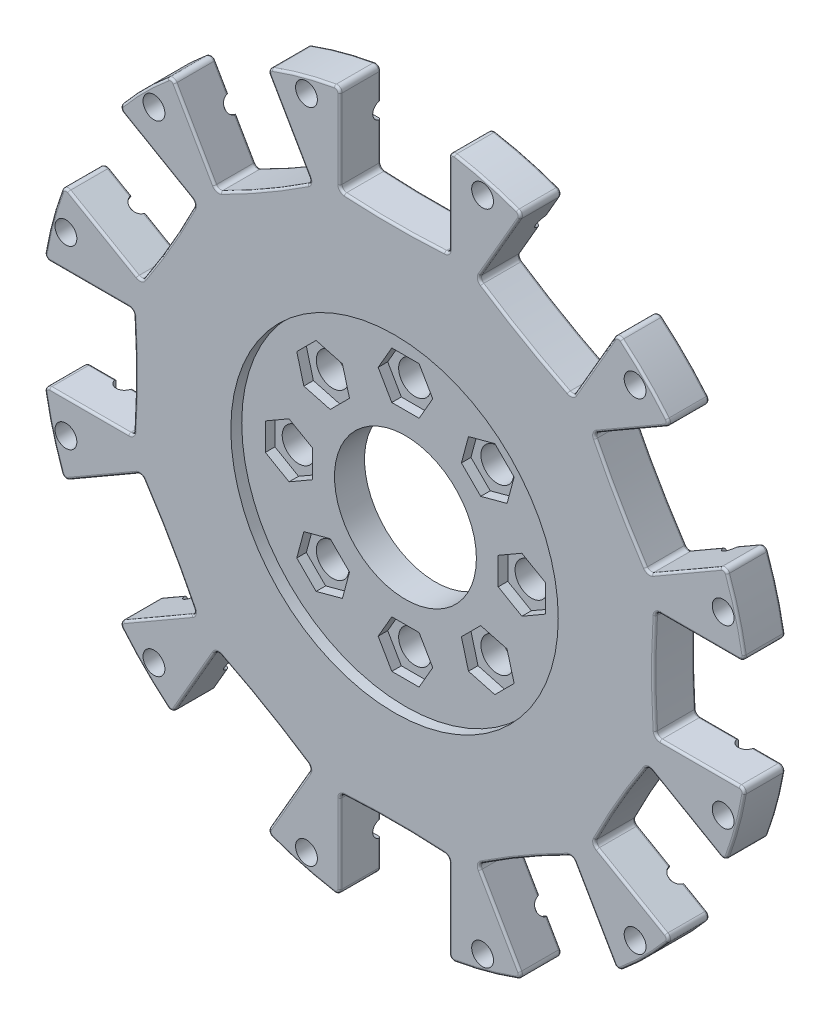
SolidWorks part; units mm, degrees
ref_plane "Front Plane" through (0, 0, 0) normal (0, 0, 1) x (1, 0, 0)
ref_plane "Top Plane" through (0, 0, 0) normal (0, 1, 0) x (1, 0, 0)
ref_plane "Right Plane" through (0, 0, 0) normal (1, 0, 0) x (0, 0, -1)
sketch "Sketch2" plane through (0, 0, 0) normal (0, 0, 1) x (1, 0, 0)
  line L0 (-10, 64.2262) -> (-10, 47.8337)
  line L1 (10, 64.2262) -> (10, 47.8337)
  line L2 (23.4528, 60.6215) -> (15.2566, 46.4252)
  line L3 (40.7733, 50.6215) -> (32.5771, 36.4252)
  line L4 (50.6215, 40.7733) -> (36.4252, 32.5771)
  line L5 (60.6215, 23.4528) -> (46.4252, 15.2566)
  line L6 (64.2262, 10) -> (47.8337, 10)
  line L7 (64.2262, -10) -> (47.8337, -10)
  line L8 (60.6215, -23.4528) -> (46.4252, -15.2566)
  line L9 (50.6215, -40.7733) -> (36.4252, -32.5771)
  line L10 (40.7733, -50.6215) -> (32.5771, -36.4252)
  line L11 (23.4528, -60.6215) -> (15.2566, -46.4252)
  line L12 (10, -64.2262) -> (10, -47.8337)
  line L13 (-10, -64.2262) -> (-10, -47.8337)
  line L14 (-23.4528, -60.6215) -> (-15.2566, -46.4252)
  line L15 (-40.7733, -50.6215) -> (-32.5771, -36.4252)
  line L16 (-50.6215, -40.7733) -> (-36.4252, -32.5771)
  line L17 (-60.6215, -23.4528) -> (-46.4252, -15.2566)
  line L18 (-64.2262, -10) -> (-47.8337, -10)
  line L19 (-64.2262, 10) -> (-47.8337, 10)
  line L20 (-60.6215, 23.4528) -> (-46.4252, 15.2566)
  line L21 (-50.6215, 40.7733) -> (-36.4252, 32.5771)
  line L22 (-40.7733, 50.6215) -> (-32.5771, 36.4252)
  line L23 (-23.4528, 60.6215) -> (-15.2566, 46.4252)
  arc A0 (-10, 64.2262) -> (-23.4528, 60.6215) centre (0, 0) ccw
  circle A1 centre (0, 0) radius 47.5
  arc A2 (-10, 47.8337) -> (10, 47.8337) centre (0, 197.5) ccw
  arc A3 (15.2566, 46.4252) -> (32.5771, 36.4252) centre (98.75, 171.04) ccw
  arc A4 (36.4252, 32.5771) -> (46.4252, 15.2566) centre (171.04, 98.75) ccw
  arc A5 (47.8337, 10) -> (47.8337, -10) centre (197.5, 0) ccw
  arc A6 (46.4252, -15.2566) -> (36.4252, -32.5771) centre (171.04, -98.75) ccw
  arc A7 (32.5771, -36.4252) -> (15.2566, -46.4252) centre (98.75, -171.04) ccw
  arc A8 (10, -47.8337) -> (-10, -47.8337) centre (0, -197.5) ccw
  arc A9 (-15.2566, -46.4252) -> (-32.5771, -36.4252) centre (-98.75, -171.04) ccw
  arc A10 (-36.4252, -32.5771) -> (-46.4252, -15.2566) centre (-171.04, -98.75) ccw
  arc A11 (-47.8337, -10) -> (-47.8337, 10) centre (-197.5, 0) ccw
  arc A12 (-46.4252, 15.2566) -> (-36.4252, 32.5771) centre (-171.04, 98.75) ccw
  arc A13 (-32.5771, 36.4252) -> (-15.2566, 46.4252) centre (-98.75, 171.04) ccw
  arc A14 (-40.7733, 50.6215) -> (-50.6215, 40.7733) centre (0, 0) ccw
  arc A15 (-60.6215, 23.4528) -> (-64.2262, 10) centre (0, 0) ccw
  arc A16 (-64.2262, -10) -> (-60.6215, -23.4528) centre (0, 0) ccw
  arc A17 (-50.6215, -40.7733) -> (-40.7733, -50.6215) centre (0, 0) ccw
  arc A18 (-23.4528, -60.6215) -> (-10, -64.2262) centre (0, 0) ccw
  arc A19 (10, -64.2262) -> (23.4528, -60.6215) centre (0, 0) ccw
  arc A20 (40.7733, -50.6215) -> (50.6215, -40.7733) centre (0, 0) ccw
  arc A21 (60.6215, -23.4528) -> (64.2262, -10) centre (0, 0) ccw
  arc A22 (64.2262, 10) -> (60.6215, 23.4528) centre (0, 0) ccw
  arc A23 (50.6215, 40.7733) -> (40.7733, 50.6215) centre (0, 0) ccw
  arc A24 (23.4528, 60.6215) -> (10, 64.2262) centre (0, 0) ccw
  point P66 (0, 0)
  dimension "D1" = 130
  dimension "D4" = 95
  dimension "D5" = 150
  dimension "D2" = 20
  dimension "D3" = 10
  dimension "D6" = 12
extrude "Boss-Extrude1" add sketch "Sketch2" along normal blind 7.5 contours A1 | L2 A24 L1 A2 A1 A3 | L4 A23 L3 A3 A1 A4 | L6 A22 L5 A4 A1 A5 | L8 A21 L7 A5 A1 A6 | L10 A20 L9 A6 A1 A7 | L12 A19 L11 A7 A1 A8 | L14 A18 L13 A8 A1 A9 | L16 A17 L15 A9 A1 A10 | L18 A16 L17 A10 A1 A11 | L20 A15 L19 A11 A1 A12 | L22 A14 L21 A12 A1 A13 | A13 A1 A2 L0 A0 L23 region at (-14.7728, 55.1327, 0) region at (14.7728, 55.1327, 0) region at (0, 0, 0) region at (40.3599, 40.3599, 0) region at (-40.3599, 40.3599, 0) region at (55.1327, 14.7728, 0) region at (-55.1327, 14.7728, 0) region at (55.1327, -14.7728, 0) region at (-55.1327, -14.7728, 0) region at (40.3599, -40.3599, 0) region at (-40.3599, -40.3599, 0) region at (14.7728, -55.1327, 0) region at (-14.7728, -55.1327, 0)
sketch "Sketch3" plane through (0, 0, 7.5) normal (0, 0, 1) x (1, 0, 0)
  line L0 (0, 0) -> (0, 47.5) construction
  line L49 (0, 0) -> (45.9619, 45.9619) construction
  line L62 (18.6194, 11.5483) -> (19.9135, 16.3779)
  line L63 (5, 21.3318) -> (2.5, 25.6619)
  line L64 (2.5, 25.6619) -> (-2.5, 25.6619)
  line L65 (-2.5, 25.6619) -> (-5, 21.3318)
  line L66 (-5, 21.3318) -> (-2.5, 17.0016)
  line L67 (-2.5, 17.0016) -> (2.5, 17.0016)
  line L68 (2.5, 17.0016) -> (5, 21.3318)
  line L69 (19.9135, 16.3779) -> (16.3779, 19.9135)
  line L70 (16.3779, 19.9135) -> (11.5483, 18.6194)
  line L71 (11.5483, 18.6194) -> (10.2542, 13.7897)
  line L72 (10.2542, 13.7897) -> (13.7897, 10.2542)
  line L73 (13.7897, 10.2542) -> (18.6194, 11.5483)
  line L74 (21.3318, -5) -> (25.6619, -2.5)
  line L75 (25.6619, -2.5) -> (25.6619, 2.5)
  line L76 (25.6619, 2.5) -> (21.3318, 5)
  line L77 (21.3318, 5) -> (17.0016, 2.5)
  line L78 (17.0016, 2.5) -> (17.0016, -2.5)
  line L79 (17.0016, -2.5) -> (21.3318, -5)
  line L80 (11.5483, -18.6194) -> (16.3779, -19.9135)
  line L81 (16.3779, -19.9135) -> (19.9135, -16.3779)
  line L82 (19.9135, -16.3779) -> (18.6194, -11.5483)
  line L83 (18.6194, -11.5483) -> (13.7897, -10.2542)
  line L84 (13.7897, -10.2542) -> (10.2542, -13.7897)
  line L85 (10.2542, -13.7897) -> (11.5483, -18.6194)
  line L86 (-5, -21.3318) -> (-2.5, -25.6619)
  line L87 (-2.5, -25.6619) -> (2.5, -25.6619)
  line L88 (2.5, -25.6619) -> (5, -21.3318)
  line L89 (5, -21.3318) -> (2.5, -17.0016)
  line L90 (2.5, -17.0016) -> (-2.5, -17.0016)
  line L91 (-2.5, -17.0016) -> (-5, -21.3318)
  line L92 (-18.6194, -11.5483) -> (-19.9135, -16.3779)
  line L93 (-19.9135, -16.3779) -> (-16.3779, -19.9135)
  line L94 (-16.3779, -19.9135) -> (-11.5483, -18.6194)
  line L95 (-11.5483, -18.6194) -> (-10.2542, -13.7897)
  line L96 (-10.2542, -13.7897) -> (-13.7897, -10.2542)
  line L97 (-13.7897, -10.2542) -> (-18.6194, -11.5483)
  line L98 (-21.3318, 5) -> (-25.6619, 2.5)
  line L99 (-25.6619, 2.5) -> (-25.6619, -2.5)
  line L100 (-25.6619, -2.5) -> (-21.3318, -5)
  line L101 (-21.3318, -5) -> (-17.0016, -2.5)
  line L102 (-17.0016, -2.5) -> (-17.0016, 2.5)
  line L103 (-17.0016, 2.5) -> (-21.3318, 5)
  line L104 (-11.5483, 18.6194) -> (-16.3779, 19.9135)
  line L105 (-16.3779, 19.9135) -> (-19.9135, 16.3779)
  line L106 (-19.9135, 16.3779) -> (-18.6194, 11.5483)
  line L107 (-18.6194, 11.5483) -> (-13.7897, 10.2542)
  line L108 (-13.7897, 10.2542) -> (-10.2542, 13.7897)
  line L109 (-10.2542, 13.7897) -> (-11.5483, 18.6194)
  circle A0 centre (0, 0) radius 30
  circle A1 centre (0, 0) radius 13
  arc A2 (-10, 47.8337) -> (10, 47.8337) centre (0, 197.5) ccw construction
  circle A3 centre (0, 21.3318) radius 5 construction
  arc A4 (50.6215, 40.7733) -> (40.7733, 50.6215) centre (0, 0) ccw construction
  circle A5 centre (44.0798, 44.0798) radius 2
  circle A6 centre (60.2141, 16.1343) radius 2
  circle A7 centre (60.2141, -16.1343) radius 2
  circle A8 centre (44.0798, -44.0798) radius 2
  circle A9 centre (16.1343, -60.2141) radius 2
  circle A10 centre (-16.1343, -60.2141) radius 2
  circle A11 centre (-44.0798, -44.0798) radius 2
  circle A12 centre (-60.2141, -16.1343) radius 2
  circle A13 centre (-60.2141, 16.1343) radius 2
  circle A14 centre (-44.0798, 44.0798) radius 2
  circle A15 centre (-16.1343, 60.2141) radius 2
  circle A16 centre (16.1343, 60.2141) radius 2
  circle A17 centre (0, 21.3318) radius 3
  circle A18 centre (15.0838, 15.0838) radius 3
  circle A19 centre (21.3318, 0) radius 3
  circle A20 centre (15.0838, -15.0838) radius 3
  circle A21 centre (0, -21.3318) radius 3
  circle A22 centre (-15.0838, -15.0838) radius 3
  circle A23 centre (-21.3318, 0) radius 3
  circle A24 centre (-15.0838, 15.0838) radius 3
  point P62 (0, 0)
  point P90 (0, 0)
  point P130 (0, 0)
  dimension "D1" = 8
  dimension "D3" = 12
extrude "Cut-Extrude1" cut sketch "Sketch3" against normal blind 3.75 contours L109 L104 L105 L106 L107 L108 | L68 L63 L64 L65 L66 L67 | L73 L62 L69 L70 L71 L72 | L76 L77 L78 L79 L74 L75 | L83 L84 L85 L80 L81 L82 | L90 L91 L86 L87 L88 L89 | L95 L96 L97 L92 L93 L94 | L102 L103 L98 L99 L100 L101
extrude "Cut-Extrude2" cut sketch "Sketch3<3>" against normal through all contours A24 | A19 | A20 | A21 | A22 | A23 | A1 | A17 | A18 | A13 | A14 | A15 | A16 | A5 | A6 | A7 | A8 | A9 | A10 | A11 | A12 region at (0, 0, 7.5) region at (21.3318, 0, 7.5) region at (15.0838, -15.0838, 7.5) region at (0, -21.3318, 7.5) region at (-15.0838, -15.0838, 7.5) region at (-21.3318, 0, 7.5) region at (-15.0838, 15.0838, 7.5)
sketch "Sketch3<3>" plane through (0, 0, 7.5) normal (0, 0, 1) x (1, 0, 0) same geometry as "Sketch3"
extrude "Cut-Extrude3" cut sketch "Sketch3<4>" against normal blind 2 contours A0
sketch "Sketch3<4>" plane through (0, 0, 7.5) normal (0, 0, 1) x (1, 0, 0) same geometry as "Sketch3"
sketch "Sketch8" plane through (0, 0, 0) normal (0, 0, -1) x (-1, 0, 0)
  line L0 (-12, 57) -> (12, 57) construction
  line L1 (-12, 57) -> (-12, 58.5)
  line L2 (-12, 58.5) -> (12, 58.5)
  line L3 (12, 58.5) -> (12, 57)
  line L4 (-12, 57) -> (12, 57)
  point P2 (0, 57)
  dimension "D1" = 24
  dimension "D2" = 57
  dimension "D3" = 1.5
revolve "Cut-Revolve2" cut sketch "Sketch8" angle 360 about L0
pattern_circular "CirPattern1" count 12 over 360 about axis through (0, 0, 0) along (0, 0, 1) of "Cut-Revolve2"
fillet "Fillet1" radius 0.9 48 edges at (64.2262, -10, 3.75) (60.6215, -23.4528, 3.75) (46.4252, -15.2566, 3.75) (36.4252, -32.5771, 3.75) (50.6215, -40.7733, 3.75) (40.7733, -50.6215, 3.75) (32.5771, -36.4252, 3.75) (15.2566, -46.4252, 3.75) (23.4528, -60.6215, 3.75) (10, -64.2262, 3.75) (10, -47.8337, 3.75) (-10, -47.8337, 3.75) (-10, -64.2262, 3.75) (-23.4528, -60.6215, 3.75) (-15.2566, -46.4252, 3.75) (-32.5771, -36.4252, 3.75) (-40.7733, -50.6215, 3.75) (-50.6215, -40.7733, 3.75) (-36.4252, -32.5771, 3.75) (-46.4252, -15.2566, 3.75) (-60.6215, -23.4528, 3.75) (-64.2262, -10, 3.75) (-47.8337, -10, 3.75) (-47.8337, 10, 3.75) (-64.2262, 10, 3.75) (-60.6215, 23.4528, 3.75) (-46.4252, 15.2566, 3.75) (-36.4252, 32.5771, 3.75) (-50.6215, 40.7733, 3.75) (-40.7733, 50.6215, 3.75) (-32.5771, 36.4252, 3.75) (-15.2566, 46.4252, 3.75) (-23.4528, 60.6215, 3.75) (-10, 64.2262, 3.75) (-10, 47.8337, 3.75) (10, 47.8337, 3.75) (10, 64.2262, 3.75) (23.4528, 60.6215, 3.75) (15.2566, 46.4252, 3.75) (32.5771, 36.4252, 3.75) (40.7733, 50.6215, 3.75) (36.4252, 32.5771, 3.75) (46.4252, 15.2566, 3.75) (60.6215, 23.4528, 3.75) (64.2262, 10, 3.75) (47.8337, 10, 3.75) (47.8337, -10, 3.75) (50.6215, 40.7733, 3.75)
fillet "Fillet2" radius 0.4 216 edges at (48.0613, -9.7555, 0) (48.0613, 9.7555, 0) (63.8548, 10.3202, 0) (60.46, 22.9898, 0) (46.5001, 15.5821, 0) (36.7445, 32.4792, 0) (32.4792, 36.7445, 0) (15.5821, 46.5001, 0) (22.9898, 60.46, 0) (10.3202, 63.8548, 0) (9.7555, 48.0613, 0) (-9.7555, 48.0613, 0) (-10.3202, 63.8548, 0) (-22.9898, 60.46, 0) (-15.5821, 46.5001, 0) (-32.4792, 36.7445, 0) (-40.865, 50.1398, 0) (-50.1398, 40.865, 0) (-36.7445, 32.4792, 0) (-46.5001, 15.5821, 0) (-60.46, 22.9898, 0) (-63.8548, 10.3202, 0) (-48.0613, 9.7555, 0) (-48.0613, -9.7555, 0) (-63.8548, -10.3202, 0) (-60.46, -22.9898, 0) (-46.5001, -15.5821, 0) (-36.7445, -32.4792, 0) (-50.1398, -40.865, 0) (-40.865, -50.1398, 0) (-32.4792, -36.7445, 0) (-15.5821, -46.5001, 0) (-22.9898, -60.46, 0) (-10.3202, -63.8548, 0) (-9.7555, -48.0613, 0) (9.7555, -48.0613, 0) (10.3202, -63.8548, 0) (22.9898, -60.46, 0) (15.5821, -46.5001, 0) (32.4792, -36.7445, 0) (40.865, -50.1398, 0) (50.1398, -40.865, 0) (36.7445, -32.4792, 0) (46.5001, -15.5821, 0) (60.46, -22.9898, 0) (63.8548, -10.3202, 0) (60.46, -22.9898, 7.5) (46.5001, -15.5821, 7.5) (36.7445, -32.4792, 7.5) (50.1398, -40.865, 7.5) (40.865, -50.1398, 7.5) (32.4792, -36.7445, 7.5) (15.5821, -46.5001, 7.5) (22.9898, -60.46, 7.5) (10.3202, -63.8548, 7.5) (9.7555, -48.0613, 7.5) (-9.7555, -48.0613, 7.5) (-10.3202, -63.8548, 7.5) (-22.9898, -60.46, 7.5) (-15.5821, -46.5001, 7.5) (-32.4792, -36.7445, 7.5) (-40.865, -50.1398, 7.5) (-50.1398, -40.865, 7.5) (-36.7445, -32.4792, 7.5) (-46.5001, -15.5821, 7.5) (-60.46, -22.9898, 7.5) (-63.8548, -10.3202, 7.5) (-48.0613, -9.7555, 7.5) (-48.0613, 9.7555, 7.5) (-63.8548, 10.3202, 7.5) (-60.46, 22.9898, 7.5) (-46.5001, 15.5821, 7.5) (-36.7445, 32.4792, 7.5) (-50.1398, 40.865, 7.5) (-40.865, 50.1398, 7.5) (-32.4792, 36.7445, 7.5) (-15.5821, 46.5001, 7.5) (-22.9898, 60.46, 7.5) (-10.3202, 63.8548, 7.5) (-9.7555, 48.0613, 7.5) (9.7555, 48.0613, 7.5) (10.3202, 63.8548, 7.5) (22.9898, 60.46, 7.5) (15.5821, 46.5001, 7.5) (32.4792, 36.7445, 7.5) (40.865, 50.1398, 7.5) (50.1398, 40.865, 7.5) (36.7445, 32.4792, 7.5) (46.5001, 15.5821, 7.5) (60.46, 22.9898, 7.5) (63.8548, 10.3202, 7.5) (48.0613, 9.7555, 7.5) (48.0613, -9.7555, 7.5) (63.8548, -10.3202, 7.5) (50.1398, 40.865, 0) (40.865, 50.1398, 0) (52.089, -10, 0) (60.8332, -10, 0) (47.5, 0, 0) (52.089, 10, 0) (60.8332, 10, 0) (62.7852, 16.8232, 0) (50.1104, 17.3842, 0) (57.6831, 21.7564, 0) (41.1362, 23.75, 0) (40.1104, 34.7047, 0) (47.6831, 39.0769, 0) (34.7047, 40.1104, 0) (39.0769, 47.6831, 0) (23.75, 41.1362, 0) (17.3842, 50.1104, 0) (21.7564, 57.6831, 0) (16.8232, 62.7852, 0) (10, 52.089, 0) (10, 60.8332, 0) (0, 47.5, 0) (-10, 52.089, 0) (-10, 60.8332, 0) (-16.8232, 62.7852, 0) (-17.3842, 50.1104, 0) (-21.7564, 57.6831, 0) (-23.75, 41.1362, 0) (-34.7047, 40.1104, 0) (-39.0769, 47.6831, 0) (-45.9619, 45.9619, 0) (-40.1104, 34.7047, 0) (-47.6831, 39.0769, 0) (-41.1362, 23.75, 0) (-50.1104, 17.3842, 0) (-57.6831, 21.7564, 0) (-62.7852, 16.8232, 0) (-52.089, 10, 0) (-60.8332, 10, 0) (-47.5, 0, 0) (-52.089, -10, 0) (-60.8332, -10, 0) (-62.7852, -16.8232, 0) (-50.1104, -17.3842, 0) (-57.6831, -21.7564, 0) (-41.1362, -23.75, 0) (-40.1104, -34.7047, 0) (-47.6831, -39.0769, 0) (-45.9619, -45.9619, 0) (-34.7047, -40.1104, 0) (-39.0769, -47.6831, 0) (-23.75, -41.1362, 0) (-17.3842, -50.1104, 0) (-21.7564, -57.6831, 0) (-16.8232, -62.7852, 0) (-10, -52.089, 0) (-10, -60.8332, 0) (0, -47.5, 0) (10, -52.089, 0) (10, -60.8332, 0) (16.8232, -62.7852, 0) (17.3842, -50.1104, 0) (21.7564, -57.6831, 0) (23.75, -41.1362, 0) (34.7047, -40.1104, 0) (39.0769, -47.6831, 0) (45.9619, -45.9619, 0) (40.1104, -34.7047, 0) (47.6831, -39.0769, 0) (41.1362, -23.75, 0) (50.1104, -17.3842, 0) (57.6831, -21.7564, 0) (62.7852, -16.8232, 0) (55.9222, -10, 7.5) (47.5, 0, 7.5) (55.9222, 10, 7.5) (62.7852, 16.8232, 7.5) (53.43, 19.3008, 7.5) (41.1362, 23.75, 7.5) (43.43, 36.6214, 7.5) (45.9619, 45.9619, 7.5) (36.6214, 43.43, 7.5) (23.75, 41.1362, 7.5) (19.3008, 53.43, 7.5) (16.8232, 62.7852, 7.5) (10, 55.9222, 7.5) (0, 47.5, 7.5) (-10, 55.9222, 7.5) (-16.8232, 62.7852, 7.5) (-19.3008, 53.43, 7.5) (-23.75, 41.1362, 7.5) (-36.6214, 43.43, 7.5) (-45.9619, 45.9619, 7.5) (-43.43, 36.6214, 7.5) (-41.1362, 23.75, 7.5) (-53.43, 19.3008, 7.5) (-62.7852, 16.8232, 7.5) (-55.9222, 10, 7.5) (-47.5, 0, 7.5) (-55.9222, -10, 7.5) (-62.7852, -16.8232, 7.5) (-53.43, -19.3008, 7.5) (-41.1362, -23.75, 7.5) (-43.43, -36.6214, 7.5) (-45.9619, -45.9619, 7.5) (-36.6214, -43.43, 7.5) (-23.75, -41.1362, 7.5) (-19.3008, -53.43, 7.5) (-16.8232, -62.7852, 7.5) (-10, -55.9222, 7.5) (0, -47.5, 7.5) (10, -55.9222, 7.5) (16.8232, -62.7852, 7.5) (19.3008, -53.43, 7.5) (23.75, -41.1362, 7.5) (36.6214, -43.43, 7.5) (45.9619, -45.9619, 7.5) (43.43, -36.6214, 7.5) (41.1362, -23.75, 7.5) (53.43, -19.3008, 7.5) (62.7852, -16.8232, 7.5) (45.9619, 45.9619, 0)
